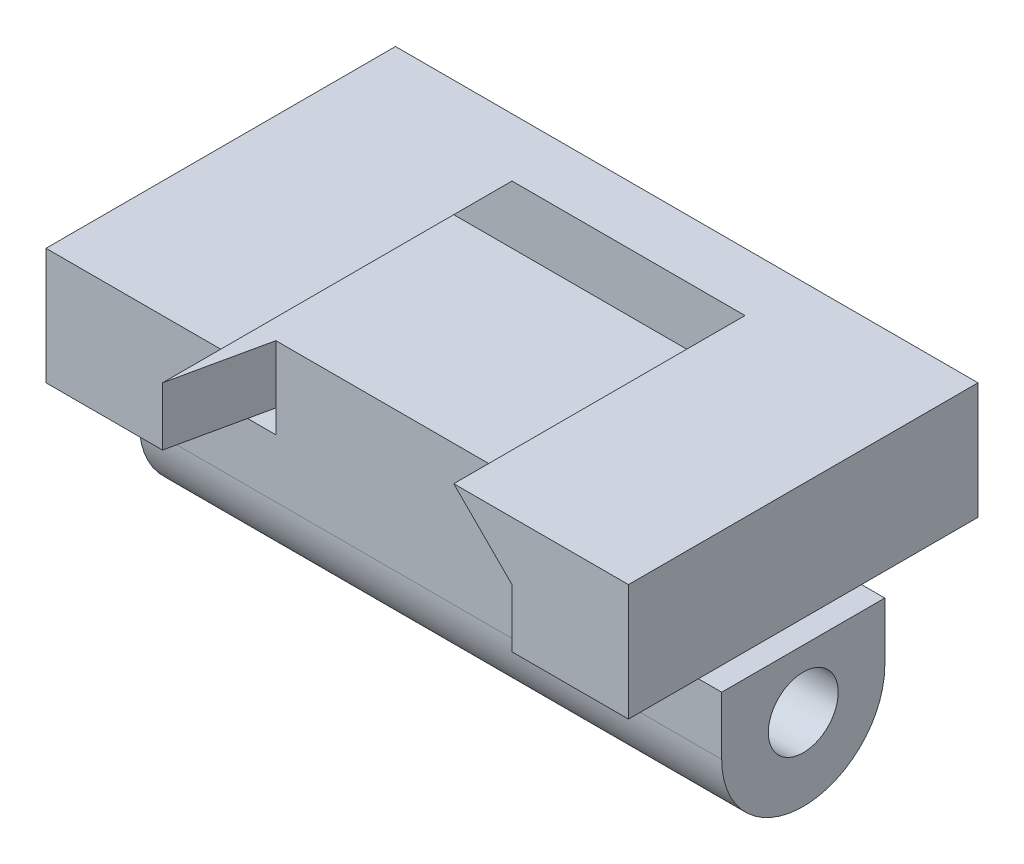
SolidWorks part; units mm, degrees
material "ABS PC"
ref_plane "Front Plane" through (0, 0, 0) normal (0, 0, 1) x (1, 0, 0)
ref_plane "Top Plane" through (0, 0, 0) normal (0, 1, 0) x (1, 0, 0)
ref_plane "Right Plane" through (0, 0, 0) normal (1, 0, 0) x (0, 0, -1)
sketch "Sketch1" plane through (0, 0, 0) normal (0, 1, 0) x (1, 0, 0)
  line L0 (0, 0) -> (0, 6.9526) construction
  line L1 (-25, 15) -> (-15, 15)
  line L2 (-25, 15) -> (-25, -15)
  line L3 (-25, -15) -> (-15, -15)
  line L4 (-15, 15) -> (-15, -15)
  line L5 (-25, 15) -> (-15, -15) construction
  line L6 (-25, -15) -> (-15, 15) construction
  line L7 (25, -15) -> (15, 15) construction
  line L8 (25, 15) -> (15, -15) construction
  line L9 (15, 15) -> (15, -15)
  line L10 (25, -15) -> (15, -15)
  line L11 (25, 15) -> (25, -15)
  line L12 (25, 15) -> (15, 15)
  line L13 (-15, 15) -> (15, 15)
  line L22 (-15, -15) -> (15, -15)
  line L23 (-15, -15) -> (-13.2665, -7)
  line L24 (-13.2665, -7) -> (13.2665, -7)
  line L25 (15, -15) -> (13.2665, -7)
  line L26 (-13.2665, 7) -> (13.2665, 7)
  circle A0 centre (0, 0) radius 15
  point P0 (-20, 0)
  point P12 (20, 0)
  point P18 (0, -7)
  dimension "D1" = 30
  dimension "D2" = 30
  dimension "D3" = 10
extrude "Boss-Extrude1" add sketch "Sketch1" along normal blind 5 contours L4 L1 L2 L3 | L11 L12 L9 L10 | L24 A0 L26 | L26 A0 | A0 L13 L4 | A0 L4 L23 | A0 L9 L13 | A0 L25 L9 region at (-20, 0, 0) region at (-11.6495, 0, -11.6495) region at (-14.4452, 0, 8.0723) region at (0, 0, 0) region at (11.6495, 0, -11.6495) region at (0, 0, -10.2867) region at (20, 0, 0) region at (14.4452, 0, 8.0723)
sketch "Sketch4" plane through (0, 0, 0) normal (0, -1, 0) x (1, 0, 0)
  line L0 (0, 0) -> (0, 7) construction
  line L1 (0, 0) -> (4.9545, 0) construction
  line L2 (-13.2665, 7) -> (13.2665, 7)
  line L3 (-13.2665, -7) -> (13.2665, -7)
  circle A0 centre (0, 0) radius 15
  point P8 (0, 7)
extrude "Boss-Extrude2" add sketch "Sketch4" along normal blind 2 contours L3 A0 L2 region at (0, 0, 0)
sketch "Sketch10" plane through (0, 0, 15) normal (0, 0, 1) x (1, 0, 0)
  line L0 (-15, 5) -> (-10, 10)
  line L1 (-25, 5) -> (-15, 5)
  line L2 (-25, 5) -> (-25, 10)
  line L3 (-25, 10) -> (-15, 10)
  line L4 (-15, 5) -> (-15, 10)
  line L5 (-10, 10) -> (-15, 10)
  line L8 (10, 10) -> (15, 10)
  line L9 (15, 5) -> (15, 10)
  line L10 (25, 10) -> (15, 10)
  line L11 (25, 5) -> (25, 10)
  line L12 (25, 5) -> (15, 5)
  line L13 (15, 5) -> (10, 10)
  line M6 (25, 5) -> (15, 5)
extrude "Boss-Extrude7" add sketch "Sketch10" against normal blind 30 contours L4 L3 L2 M6 | L0 L5 L4 | L13 L9 L8 | L11 L10 L9 M6 region at (-13.3333, 8.3333, 15) region at (-20, 7.5, 15) region at (13.3333, 8.3333, 15) region at (20, 7.5, 15)
sketch "Sketch11" plane through (25, 0, 0) normal (1, 0, 0) x (0, 0, -1)
  line L0 (0, 0) -> (0, -7) construction
  line L1 (15, 0) -> (-15, 0) construction
  line L2 (-7, -7) -> (-7, -2)
  line L3 (-7, -2) -> (7, -2)
  line L4 (7, -2) -> (7, -7)
  circle A0 centre (0, -7) radius 3
  arc A1 (-7, -7) -> (7, -7) centre (0, -7) ccw
extrude "Boss-Extrude8" add sketch "Sketch11" against normal blind 50
sketch "Sketch12" plane through (0, 0, -15) normal (0, 0, -1) x (-1, 0, 0)
  line L0 (-15, 5) -> (15, 5)
  line L1 (15, 5) -> (10, 10)
  line L2 (10, 10) -> (-10, 10)
  line L3 (-10, 10) -> (-15, 5)
extrude "Boss-Extrude9" add sketch "Sketch12" against normal blind 5
